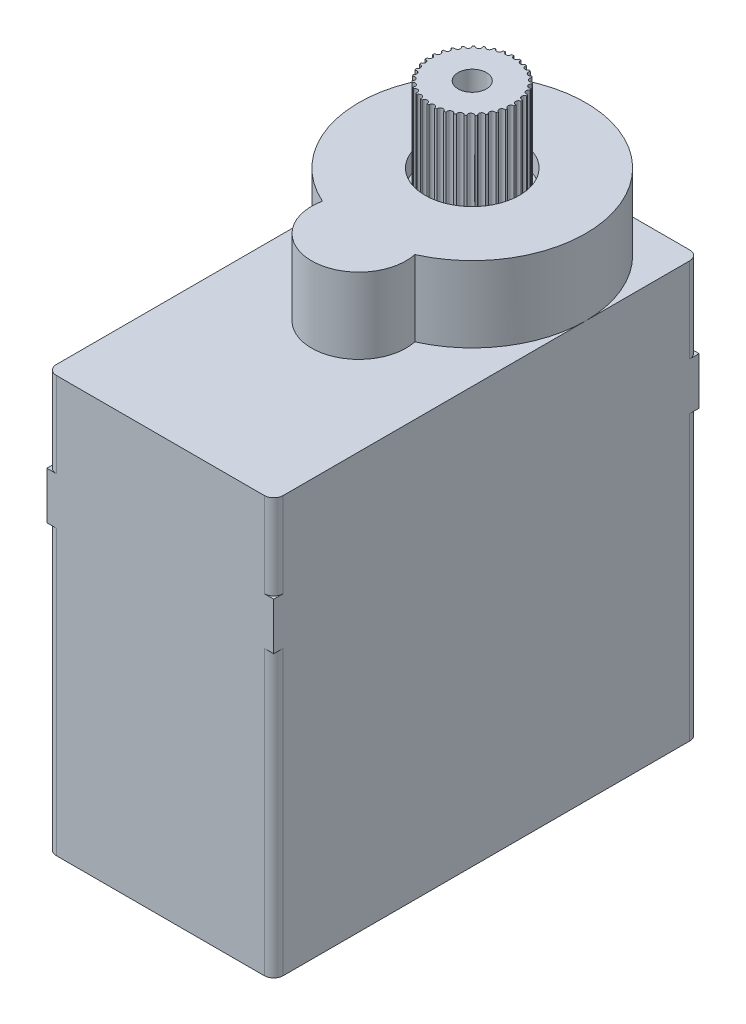
SolidWorks part; units mm, degrees
material "Custom Plastic"
ref_plane "Ön Düzlem" through (0, 0, 0) normal (0, 0, 1) x (1, 0, 0)
ref_plane "Üst Düzlem" through (0, 0, 0) normal (0, 1, 0) x (1, 0, 0)
ref_plane "Sağ Düzlem" through (0, 0, 0) normal (1, 0, 0) x (0, 0, -1)
sketch "Çizim1" plane through (0, 0, 0) normal (0, 1, 0) x (1, 0, 0)
  line L1 (-5.5, 11.25) -> (5.5, 11.25)
  line L2 (-6, 10.75) -> (-6, -10.75)
  line L3 (-5.5, -11.25) -> (5.5, -11.25)
  line L4 (6, 10.75) -> (6, -10.75)
  line L5 (-6, 11.25) -> (6, -11.25) construction
  line L6 (-6, -11.25) -> (6, 11.25) construction
  arc A0 (5.5, -11.25) -> (6, -10.75) centre (5.5, -10.75) ccw
  arc A1 (-6, -10.75) -> (-5.5, -11.25) centre (-5.5, -10.75) ccw
  arc A2 (5.5, 11.25) -> (6, 10.75) centre (5.5, 10.75) cw
  arc A3 (-5.5, 11.25) -> (-6, 10.75) centre (-5.5, 10.75) ccw
  point P0 (0, 0)
  dimension "D3" = 0.5
  dimension "D1" = 12
  dimension "D2" = 22.5
extrude "Yükseklik-Ekstrüzyon1" add sketch "Çizim1" along normal blind 1
sketch "Çizim2" plane through (0, 1, 0) normal (0, 1, 0) x (1, 0, 0)
  line L0 (-5, 9.25) -> (-5, -9.25)
  line L1 (-5.5, 11.25) -> (5.5, 11.25)
  line L2 (-6, 10.75) -> (-6, -10.75)
  line L3 (-5.5, -11.25) -> (5.5, -11.25)
  line L4 (6, 10.75) -> (6, -10.75)
  line L5 (-6, 11.25) -> (-5.8961, 11.0552) construction
  line L6 (-6, -11.25) -> (-5.8961, -11.0552) construction
  line L7 (-4, -10.25) -> (4, -10.25)
  line L8 (5, 9.25) -> (5, -9.25)
  line L9 (-4, 10.25) -> (4, 10.25)
  line L10 (-6, -11.25) -> (6, -11.25) construction
  line L11 (6, 11.25) -> (6, -11.25) construction
  line L12 (-6, 11.25) -> (-6, -11.25) construction
  line L13 (-6, 11.25) -> (6, 11.25) construction
  line L14 (-5, 10.25) -> (5, 10.25) construction
  line L15 (-5, 10.25) -> (-5, -10.25) construction
  line L16 (-4.9345, 9.2521) -> (4.9345, -9.2521) construction
  line L17 (5, 10.25) -> (5, -10.25) construction
  line L18 (5.8961, 11.0552) -> (6, 11.25) construction
  line L19 (-5, -10.25) -> (5, -10.25) construction
  line L20 (5.8961, -11.0552) -> (6, -11.25) construction
  line L21 (-4.9345, -9.2521) -> (4.9345, 9.2521) construction
  arc A0 (5.5, -11.25) -> (6, -10.75) centre (5.5, -10.75) ccw
  arc A1 (-6, -10.75) -> (-5.5, -11.25) centre (-5.5, -10.75) ccw
  arc A2 (5.5, 11.25) -> (6, 10.75) centre (5.5, 10.75) cw
  arc A3 (-5.5, 11.25) -> (-6, 10.75) centre (-5.5, 10.75) ccw
  arc A5 (4, 10.25) -> (5, 9.25) centre (5, 10.25) ccw
  arc A7 (-4, -10.25) -> (-5, -9.25) centre (-5, -10.25) ccw
  arc A8 (-5, 9.25) -> (-4, 10.25) centre (-5, 10.25) ccw
  arc A9 (5, -9.25) -> (4, -10.25) centre (5, -10.25) ccw
  point P0 (0, 0)
  dimension "D2" = 0.5
  dimension "D1" = 1
extrude "Yükseklik-Ekstrüzyon2" add sketch "Çizim2" along normal blind 5
sketch "Çizim3" plane through (0, 6, 0) normal (0, 1, 0) x (1, 0, 0)
  line L0 (0, -10.25) -> (0, -11.25) construction
  line L1 (-4, -10.25) -> (4, -10.25) construction
  line L2 (-5.5, -11.25) -> (5.5, -11.25) construction
  line L3 (0, -11.25) -> (0, -10.75) construction
  line L4 (0, -10.75) -> (2.4368, -10.75) construction
  line L6 (-2, -10.25) -> (2, -10.25)
  line L7 (-2, -10.25) -> (-2, -11.25)
  line L8 (-2, -11.25) -> (2, -11.25)
  line L9 (2, -10.25) -> (2, -11.25)
  line L10 (-2, -10.25) -> (2, -11.25) construction
  line L11 (-2, -11.25) -> (2, -10.25) construction
  dimension "D1" = 4
extrude "Kes-Ekstrüzyon1" cut sketch "Çizim3" against normal blind 1
fillet "Radyus1" radius 0.1 2 edges at (2, 5, 10.75) (-2, 5, 10.75)
sketch "Çizim4" plane through (0, 6, 0) normal (0, 1, 0) x (1, 0, 0)
  line L0 (-4, 10.25) -> (4, 10.25)
  line L1 (-5.5, 11.25) -> (5.5, 11.25)
  line L2 (-6, 10.75) -> (-6, -10.75)
  line L3 (-5.5, -11.25) -> (5.5, -11.25)
  line L4 (6, 10.75) -> (6, -10.75)
  line L5 (-6, 11.25) -> (-5.8961, 11.0552) construction
  line L6 (-6, -11.25) -> (-5.8961, -11.0552) construction
  line L7 (-4, 10.25) -> (4, 10.25)
  line L8 (5, 9.25) -> (5, -9.25)
  line L9 (5, -9.25) -> (5, 9.25)
  line L10 (-4, 10.25) -> (4, 10.25)
  line L11 (5, 9.25) -> (5, -9.25)
  line L12 (-4, -10.25) -> (4, -10.25)
  line L13 (-5, 9.25) -> (-5, -9.25)
  line L14 (-4.9345, 9.2521) -> (4.9345, -9.2521) construction
  line L15 (-5, 10.25) -> (-5, -10.25) construction
  line L16 (-5, 10.25) -> (5, 10.25) construction
  line L17 (5, 10.25) -> (5, -10.25) construction
  line L18 (5.8961, 11.0552) -> (6, 11.25) construction
  line L19 (5.8961, -11.0552) -> (6, -11.25) construction
  line L20 (-5, -10.25) -> (5, -10.25) construction
  line L21 (-4.9345, -9.2521) -> (4.9345, 9.2521) construction
  arc A0 (5.5, -11.25) -> (6, -10.75) centre (5.5, -10.75) ccw
  arc A1 (-6, -10.75) -> (-5.5, -11.25) centre (-5.5, -10.75) ccw
  arc A2 (5.5, 11.25) -> (6, 10.75) centre (5.5, 10.75) cw
  arc A3 (-5.5, 11.25) -> (-6, 10.75) centre (-5.5, 10.75) ccw
  arc A4 (-5, 9.25) -> (-4, 10.25) centre (-5, 10.25) ccw
  arc A5 (4, 10.25) -> (5, 9.25) centre (5, 10.25) ccw
  arc A6 (-4, -10.25) -> (-5, -9.25) centre (-5, -10.25) ccw
  arc A7 (5, -9.25) -> (4, -10.25) centre (5, -10.25) ccw
  arc A8 (5, 10.25) -> (5, 10.25) centre (5, 10.25) cw
  arc A9 (5, -10.25) -> (5, -10.25) centre (5, -10.25) ccw
  arc A10 (-5, -10.25) -> (-5, -10.25) centre (-5, -10.25) ccw
  arc A11 (-5, 10.25) -> (-5, 10.25) centre (-5, 10.25) ccw
  point P0 (0, 0)
  line M12 (4, -10.25) -> (2, -10.25)
  line M14 (2, -11.25) -> (5.5, -11.25)
  arc M15 (5.5, -11.25) -> (6, -10.75) centre (5.5, -10.75) ccw
  line M16 (6, -10.75) -> (6, 10.75)
  arc M17 (6, 10.75) -> (5.5, 11.25) centre (5.5, 10.75) ccw
  line M18 (5.5, 11.25) -> (-5.5, 11.25)
  arc M19 (-5.5, 11.25) -> (-6, 10.75) centre (-5.5, 10.75) ccw
  line M20 (-6, 10.75) -> (-6, -10.75)
  arc M21 (-6, -10.75) -> (-5.5, -11.25) centre (-5.5, -10.75) ccw
  line M22 (-5.5, -11.25) -> (-2, -11.25)
  line M24 (-2, -10.25) -> (-4, -10.25)
  arc M25 (-4, -10.25) -> (-5, -9.25) centre (-5, -10.25) ccw
  line M26 (-5, -9.25) -> (-5, 9.25)
  arc M27 (-5, 9.25) -> (-4, 10.25) centre (-5, 10.25) ccw
  line M28 (-4, 10.25) -> (4, 10.25)
  arc M29 (4, 10.25) -> (5, 9.25) centre (5, 10.25) ccw
  line M30 (5, 9.25) -> (5, -9.25)
  arc M31 (5, -9.25) -> (4, -10.25) centre (5, -10.25) ccw
  dimension "D1" = 0.5
  dimension "D2" = 1
extrude "Yükseklik-Ekstrüzyon4" add sketch "Çizim4" along normal blind 9 contours M31 M12 M14 M15 M16 M17 M18 M19 M20 M21 M22 M24 M25 M26 M27 M28 M29 M30 | L12 L3 region at (0, 6, -10.995)
sketch "Çizim6" plane through (0, 15, 0) normal (0, 1, 0) x (1, 0, 0)
  line L0 (-4.2188, 11.25) -> (4.2188, -11.25) construction
  line L2 (-6, 11.25) -> (-6, -11.25)
  line L4 (6, 11.25) -> (6, -11.25)
  line L6 (-3.8438, -10.25) -> (4.2188, 11.25) construction
  line L7 (-4, 10.25) -> (4, 10.25)
  line L8 (-5, 9.25) -> (-5, -9.25)
  line L9 (-4, -10.25) -> (4, -10.25)
  line L10 (5, 9.25) -> (5, -9.25)
  line L11 (-4.5616, 9.3512) -> (4.5616, -9.3512) construction
  line L12 (-4.5616, -9.3512) -> (4.5616, 9.3512) construction
  line L14 (-5.5, -11.25) -> (5.5, -11.25) construction
  line L15 (0, -11.25) -> (6, -11.25) construction
  line L20 (0, 0) -> (5, 0) construction
  line L24 (6, 11.25) -> (-6, 11.25)
  line L25 (6, -11.25) -> (-6, -11.25)
  arc A0 (-5, 9.25) -> (-4, 10.25) centre (-5, 10.25) ccw
  arc A1 (4, 10.25) -> (5, 9.25) centre (5, 10.25) ccw
  arc A2 (5, -9.25) -> (4, -10.25) centre (5, -10.25) ccw
  arc A3 (-4, -10.25) -> (-5, -9.25) centre (-5, -10.25) ccw
  point P0 (0, 0)
  point P6 (0, 0)
  point P54 (0.5, -16)
extrude "Yükseklik-Ekstrüzyon5" add sketch "Çizim6" along normal blind 2.5
sketch "Çizim7" plane through (0, 17.5, 0) normal (0, 1, 0) x (1, 0, 0)
  line L0 (6, -11.25) -> (6, 11.25) construction
  line L1 (-5.5, 11.25) -> (5.5, 11.25)
  line L2 (-6, 10.75) -> (-6, -10.75)
  line L3 (-5.5, -11.25) -> (5.5, -11.25)
  line L4 (6, 10.75) -> (6, -10.75)
  line L5 (-6, 11.25) -> (-5.8961, 11.0552) construction
  line L6 (-6, -11.25) -> (-5.8961, -11.0552) construction
  line L7 (-5, 9.25) -> (-5, -9.25)
  line L8 (-4, 10.25) -> (4, 10.25)
  line L9 (5, 9.25) -> (5, -9.25)
  line L10 (4, -10.25) -> (-4, -10.25)
  line L12 (-4.9345, 9.2521) -> (4.9345, -9.2521) construction
  line L13 (5.8961, 11.0552) -> (6, 11.25) construction
  line L14 (5.8961, -11.0552) -> (6, -11.25) construction
  line L15 (-5, -9.25) -> (-5, 9.25)
  line L16 (-4.9345, -9.2521) -> (4.9345, 9.2521) construction
  line L17 (-5, 9.25) -> (-5, -9.25)
  arc A0 (-6, -10.75) -> (-5.5, -11.25) centre (-5.5, -10.75) ccw
  arc A1 (5.5, -11.25) -> (6, -10.75) centre (5.5, -10.75) ccw
  arc A2 (5.5, 11.25) -> (6, 10.75) centre (5.5, 10.75) cw
  arc A3 (-5.5, 11.25) -> (-6, 10.75) centre (-5.5, 10.75) ccw
  arc A4 (-5, 9.25) -> (-4, 10.25) centre (-5, 10.25) ccw
  arc A5 (4, 10.25) -> (5, 9.25) centre (5, 10.25) ccw
  arc A6 (5, -9.25) -> (4, -10.25) centre (5, -10.25) ccw
  arc A8 (-4, -10.25) -> (-5, -9.25) centre (-5, -10.25) ccw
  point P0 (0, 0)
  line M16 (6, -11.25) -> (6, 11.25)
  line M28 (-6, 11.25) -> (-6, -11.25)
  line M39 (-5, -9.25) -> (-5, 9.25)
  arc M40 (-5, 9.25) -> (-4, 10.25) centre (-5, 10.25) ccw
  line M41 (-4, 10.25) -> (4, 10.25)
  arc M42 (4, 10.25) -> (5, 9.25) centre (5, 10.25) ccw
  line M43 (5, 9.25) -> (5, -9.25)
  arc M44 (5, -9.25) -> (4, -10.25) centre (5, -10.25) ccw
  line M45 (4, -10.25) -> (-4, -10.25)
  arc M46 (-4, -10.25) -> (-5, -9.25) centre (-5, -10.25) ccw
  dimension "D2" = 0.5
  dimension "D1" = 22.5
extrude "Yükseklik-Ekstrüzyon6" add sketch "Çizim7" along normal blind 3.5 contours L1 A3 A0 L3 A1 A2 M28 M16 M46 M39 M40 M41 M42 M43 M44 M45 region at (0, 17.5, -10.995)
sketch "Çizim8" plane through (0, 21, 0) normal (0, 1, 0) x (1, 0, 0)
  line L0 (6, -11.25) -> (6, -10.75) construction
  line L1 (-5.5, 11.25) -> (5.5, 11.25)
  line L2 (-6, 10.75) -> (-6, -10.75)
  line L3 (-5.5, -11.25) -> (5.5, -11.25)
  line L4 (6, 10.75) -> (6, -10.75)
  line L5 (-6, 11.25) -> (6, -11.25) construction
  line L6 (-6, -11.25) -> (6, 11.25) construction
  arc A0 (-6, -10.75) -> (-5.5, -11.25) centre (-5.5, -10.75) ccw
  arc A1 (5.5, -11.25) -> (6, -10.75) centre (5.5, -10.75) ccw
  arc A2 (5.5, 11.25) -> (6, 10.75) centre (5.5, 10.75) cw
  arc A3 (-5.5, 11.25) -> (-6, 10.75) centre (-5.5, 10.75) ccw
  point P0 (0, 0)
  dimension "D1" = 0.5
extrude "Yükseklik-Ekstrüzyon7" add sketch "Çizim8" along normal blind 1
sketch "Çizim9" plane through (0, 22, 0) normal (0, 1, 0) x (1, 0, 0)
  line L0 (-6, 5.25) -> (6, 5.25) construction
  line L1 (-6, 10.75) -> (-6, -10.75) construction
  line L2 (6, -10.75) -> (6, 10.75) construction
  line L3 (5.5, 11.25) -> (-5.5, 11.25) construction
  line L4 (0, 5.25) -> (0, -0.75) construction
  arc A0 (2.4451, -0.2292) -> (-2.4451, -0.2292) centre (0, 5.25) ccw
  arc A1 (-2.4451, -0.2292) -> (2.4451, -0.2292) centre (0, -0.75) ccw
  arc A2 (1.0153, 0.3542) -> (-1.0153, 0.3542) centre (0, 5.25) ccw
  arc A3 (-1.0153, 0.3542) -> (1.0153, 0.3542) centre (0, -0.75) ccw
  dimension "D2" = 5
  dimension "D1" = 6
  dimension "D3" = 1
extrude "Kes-Ekstrüzyon2" cut sketch "Çizim9" against normal blind 1 contours A2 A3
extrude "Yükseklik-Ekstrüzyon8" add sketch "Çizim9<3>" along normal blind 3
sketch "Çizim9<3>" plane through (0, 22, 0) normal (0, 1, 0) x (1, 0, 0) same geometry as "Çizim9"
fillet "Radyus2" radius 0.5 2 edges at (1.0153, 23, -0.3542) (-1.0153, 23, -0.3542)
sketch "Çizim10" plane through (0, 25, 0) normal (0, 1, 0) x (1, 0, 0)
  arc A0 (2.4451, -0.2292) -> (-2.4451, -0.2292) centre (0, 5.25) ccw
  arc A1 (-2.4451, -0.2292) -> (2.4451, -0.2292) centre (0, -0.75) ccw
extrude "Yükseklik-Ekstrüzyon9" add sketch "Çizim10" along normal blind 1
sketch "Çizim11" plane through (0, 26, 0) normal (0, 1, 0) x (1, 0, 0)
  circle A0 centre (0, 5.25) radius 2.5
  dimension "D1" = 5
extrude "Kes-Ekstrüzyon3" cut sketch "Çizim11" against normal blind 10
sketch "Çizim15" plane through (0, 26, 0) normal (0, 1, 0) x (1, 0, 0)
  circle A0 centre (0, -0.75) radius 0.25
  dimension "D1" = 0.5
extrude "Yükseklik-Ekstrüzyon12" add sketch "Çizim15" against normal blind 11
ref_plane "Düzlem3" through (0, 30, 0) normal (0, 1, 0) x (1, 0, 0)
sketch "Çizim19" plane through (0, 30, 0) normal (0, 1, 0) x (1, 0, 0)
  circle A0 centre (0, 5.25) radius 2.25
  dimension "D1" = 4.5
extrude "Yükseklik-Ekstrüzyon17" add sketch "Çizim19" against normal blind 5 separate body
sketch "Çizim20" plane through (0, 25, 0) normal (0, -1, 0) x (1, 0, 0)
  circle A0 centre (0, -5.25) radius 4.75
  dimension "D1" = 9.5
extrude "Yükseklik-Ekstrüzyon18" add sketch "Çizim20" along normal blind 3
sketch "Çizim21" plane through (0, 30, 0) normal (0, 1, 0) x (1, 0, 0)
  circle A0 centre (0, 5.25) radius 0.75
  dimension "D1" = 1.5
extrude "Kes-Ekstrüzyon5" cut sketch "Çizim21" against normal blind 10
ref_plane "Düzlem4" through (0, 25.5, 0) normal (0, 1, 0) x (1, 0, 0)
sketch "Çizim22" plane through (0, 25.5, 0) normal (0, 1, 0) x (1, 0, 0)
  line L0 (0, 11.25) -> (0, -3.25) construction
  arc A0 (2.4451, -0.2292) -> (-2.4451, -0.2292) centre (0, 5.25) ccw construction
  arc A1 (-2.4451, -0.2292) -> (2.4451, -0.2292) centre (0, -0.75) ccw construction
  circle A2 centre (0, -0.75) radius 0.5
  dimension "D1" = 1
extrude "Yükseklik-Ekstrüzyon19" add sketch "Çizim22" against normal blind 5
sketch "Çizim23" plane through (0, 20.5, 0) normal (0, -1, 0) x (1, 0, 0)
  circle A0 centre (0, 0.75) radius 4
  dimension "D1" = 8
extrude "Yükseklik-Ekstrüzyon20" add sketch "Çizim23" along normal blind 2
sketch "Çizim24" plane through (0, 22, 0) normal (0, -1, 0) x (1, 0, 0)
  circle A0 centre (0, -5.25) radius 0.75
extrude "Yükseklik-Ekstrüzyon21" add sketch "Çizim24" along normal blind 7 separate body
ref_plane "Düzlem5" through (0, 19, 0) normal (0, -1, 0) x (-1, 0, 0)
sketch "Çizim25" plane through (0, 19, 0) normal (0, -1, 0) x (-1, 0, 0)
  circle A0 centre (0, 5.25) radius 3.5
  dimension "D1" = 7
extrude "Yükseklik-Ekstrüzyon22" add sketch "Çizim25" along normal blind 1
ref_plane "Düzlem6" through (0, 17.5, 0) normal (0, -1, 0) x (-1, 0, 0)
sketch "Çizim26" plane through (0, 17.5, 0) normal (0, -1, 0) x (-1, 0, 0)
  circle A0 centre (0, -0.75) radius 4.5
  dimension "D1" = 9
extrude "Yükseklik-Ekstrüzyon23" add sketch "Çizim26" along normal blind 1
sketch "Çizim32" plane through (0, 0, 10.25) normal (0, 0, -1) x (-1, 0, 0)
  line L1 (2, 6) -> (-2, 6)
  line L2 (2, 6) -> (2, 5.1)
  line L3 (1.9, 5) -> (-1.9, 5)
  line L4 (-2, 6) -> (-2, 5.1)
  arc A0 (-1.9, 5) -> (-2, 5.1) centre (-1.9, 5.1) cw
  arc A1 (2, 5.1) -> (1.9, 5) centre (1.9, 5.1) cw
  point P7 (-2, 5)
  dimension "D3" = 0.1
  dimension "D1" = 1
  dimension "D2" = 4
extrude "Kes-Ekstrüzyon7" cut sketch "Çizim32" along normal blind 30
sketch "Çizim33" plane through (0, 0, 11.25) normal (0, 0, 1) x (1, 0, 0)
  line L1 (-2, 6) -> (2, 6)
  line L2 (-2, 6) -> (-2, 5.1)
  line L3 (-1.9, 5) -> (1.9, 5)
  line L4 (2, 6) -> (2, 5.1)
  arc A0 (1.9, 5) -> (2, 5.1) centre (1.9, 5.1) ccw
  arc A1 (-2, 5.1) -> (-1.9, 5) centre (-1.9, 5.1) ccw
  point P7 (2, 5)
  point P10 (-2, 5)
  dimension "D3" = 0.1
  dimension "D1" = 1
  dimension "D2" = 4
extrude "Yükseklik-Ekstrüzyon33" add sketch "Çizim33" against normal blind 1
sketch "Çizim34" plane through (0, 1, 0) normal (0, 1, 0) x (1, 0, 0)
  line L0 (-5, -6.25) -> (5, -6.25) construction
  line L1 (-5, 9.25) -> (-5, -9.25) construction
  line L2 (5, -9.25) -> (5, 9.25) construction
  line L3 (-4, -10.25) -> (4, -10.25) construction
  line L5 (-3, -3.25) -> (3, -3.25)
  line L6 (-4, -4.25) -> (-4, -8.25)
  line L7 (-3, -9.25) -> (3, -9.25)
  line L8 (4, -4.25) -> (4, -8.25)
  line L9 (-4, -3.25) -> (4, -9.25) construction
  line L10 (-4, -9.25) -> (4, -3.25) construction
  arc A0 (3, -9.25) -> (4, -8.25) centre (3, -8.25) ccw
  arc A1 (-4, -8.25) -> (-3, -9.25) centre (-3, -8.25) ccw
  arc A2 (3, -3.25) -> (4, -4.25) centre (3, -4.25) cw
  arc A3 (-3, -3.25) -> (-4, -4.25) centre (-3, -4.25) ccw
  point P8 (0, -6.25)
  dimension "D4" = 1
  dimension "D1" = 4
  dimension "D2" = 6
  dimension "D3" = 8
extrude "Yükseklik-Ekstrüzyon34" add sketch "Çizim34" along normal blind 14
ref_plane "Düzlem8" through (0, 1, 0) normal (0, -1, 0) x (-1, 0, 0)
sketch "Çizim37" plane through (0, 1, 0) normal (0, -1, 0) x (-1, 0, 0)
  line L0 (4, -6.25) -> (-4, -6.25) construction
  line L1 (4, -4.25) -> (4, -8.25) construction
  line L2 (-4, -8.25) -> (-4, -4.25) construction
  line L4 (4, -9.25) -> (-4, -9.25)
  line L5 (4, -9.25) -> (4, -3.25)
  line L6 (4, -3.25) -> (-4, -3.25)
  line L7 (-4, -9.25) -> (-4, -3.25)
  line L8 (4, -9.25) -> (-4, -3.25) construction
  line L9 (4, -3.25) -> (-4, -9.25) construction
  point P6 (0, -6.25)
  dimension "D1" = 6
  dimension "D2" = 8
extrude "Yükseklik-Ekstrüzyon36" add sketch "Çizim37" against normal blind 1
ref_plane "Düzlem9" through (0, 0, -10.75) normal (0, 0, -1) x (-1, 0, 0)
sketch "Çizim39" plane through (0, 0, -10.75) normal (0, 0, -1) x (-1, 0, 0)
  line L0 (0, 0) -> (0, 6.0146) construction
  line L1 (-5.5, 0) -> (5.5, 0) construction
  line L2 (-2, 6.0146) -> (2, 6.0146)
  line L4 (-2, 6.0146) -> (-2, 5.0146)
  line L5 (-2, 5.0146) -> (2, 5.0146)
  line L6 (2, 6.0146) -> (2, 5.0146)
  line L7 (0, 6.0146) -> (2, 5.0146) construction
  line L8 (-2, 5.0146) -> (0, 6.0146) construction
extrude "Yükseklik-Ekstrüzyon37" add sketch "Çizim39" along normal blind 0.1
sketch "Çizim40" plane through (0, 0, -10.85) normal (0, 0, -1) x (-1, 0, 0)
  line L0 (-2, 5.55) -> (2, 5.55) construction
  line L1 (-2, 6) -> (-2, 5.1) construction
  line L2 (2, 5.1) -> (2, 6) construction
  circle A0 centre (0, 5.55) radius 0.4
  circle A1 centre (1, 5.55) radius 0.4
  circle A2 centre (-1, 5.55) radius 0.4
  dimension "D1" = 0.8
  dimension "D2" = 1
  dimension "D3" = 1
extrude "Yükseklik-Ekstrüzyon38" add sketch "Çizim40" along normal blind 2
sketch "Çizim41" plane through (0, 30, 0) normal (0, 1, 0) x (1, 0, 0)
  line L0 (0, 5.25) -> (-2.25, 5.25) construction
  circle A0 centre (0, 5.25) radius 2.25
  circle A1 centre (-2.25, 5.25) radius 0.15
  circle A2 centre (-2.2138, 5.6518) radius 0.15
  circle A3 centre (-2.1065, 6.0406) radius 0.15
  circle A4 centre (-1.9315, 6.404) radius 0.15
  circle A5 centre (-1.6944, 6.7304) radius 0.15
  circle A6 centre (-1.4029, 7.0091) radius 0.15
  circle A7 centre (-1.0662, 7.2313) radius 0.15
  circle A8 centre (-0.6953, 7.3899) radius 0.15
  circle A9 centre (-0.302, 7.4796) radius 0.15
  circle A10 centre (0.1009, 7.4977) radius 0.15
  circle A11 centre (0.5007, 7.4436) radius 0.15
  circle A12 centre (0.8843, 7.3189) radius 0.15
  circle A13 centre (1.2395, 7.1278) radius 0.15
  circle A14 centre (1.5549, 6.8763) radius 0.15
  circle A15 centre (1.8203, 6.5725) radius 0.15
  circle A16 centre (2.0272, 6.2262) radius 0.15
  circle A17 centre (2.1689, 5.8486) radius 0.15
  circle A18 centre (2.2409, 5.4517) radius 0.15
  circle A19 centre (2.2409, 5.0483) radius 0.15
  circle A20 centre (2.1689, 4.6514) radius 0.15
  circle A21 centre (2.0272, 4.2738) radius 0.15
  circle A22 centre (1.8203, 3.9275) radius 0.15
  circle A23 centre (1.5549, 3.6237) radius 0.15
  circle A24 centre (1.2395, 3.3722) radius 0.15
  circle A25 centre (0.8843, 3.1811) radius 0.15
  circle A26 centre (0.5007, 3.0564) radius 0.15
  circle A27 centre (0.1009, 3.0023) radius 0.15
  circle A28 centre (-0.302, 3.0204) radius 0.15
  circle A29 centre (-0.6953, 3.1101) radius 0.15
  circle A30 centre (-1.0662, 3.2687) radius 0.15
  circle A31 centre (-1.4029, 3.4909) radius 0.15
  circle A32 centre (-1.6944, 3.7696) radius 0.15
  circle A33 centre (-1.9315, 4.096) radius 0.15
  circle A34 centre (-2.1065, 4.4594) radius 0.15
  circle A35 centre (-2.2138, 4.8482) radius 0.15
  point P75 (0, 5.25)
  circle M3 centre (0, 5.25) radius 2.25
  dimension "D1" = 0.3
  dimension "D2" = 35
extrude "Kes-Ekstrüzyon8" cut sketch "Çizim41" against normal blind 5 contours A1 A0 M3 | A1 L0 A0 | L0 A1 M3 | A3 | A2 | A35 | A34 | A33 | A32 | A31 | A30 | A29 | A28 | A27 | A26 | A25 | A24 | A23 | A22 | A21 | A20 | A19 | A18 | A17 | A16 | A15 | A14 | A13 | A12 | A11 | A10 | A9 | A8 | A7 | A6 | A5 | A4 region at (-2.1854, 30, -5.187) region at (-2.1854, 30, -5.313) region at (-2.3128, 30, -5.25)
